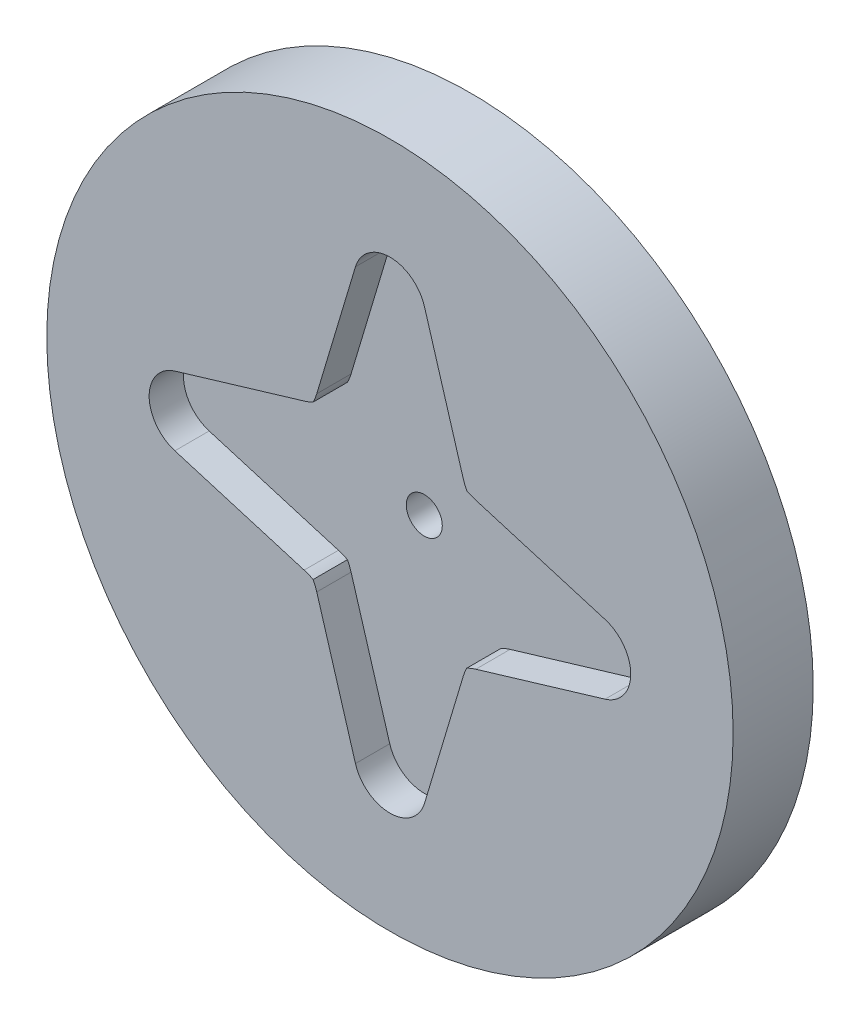
SolidWorks part; units mm, degrees
ref_plane "Front Plane" through (0, 0, 0) normal (0, 0, 1) x (1, 0, 0)
ref_plane "Top Plane" through (0, 0, 0) normal (0, 1, 0) x (1, 0, 0)
ref_plane "Right Plane" through (0, 0, 0) normal (1, 0, 0) x (0, 0, -1)
sketch "Sketch1" plane through (0, 0, 0) normal (0, 0, 1) x (1, 0, 0)
  line L0 (-11.3663, 0) -> (11.3663, 0) construction
  line L1 (-11.9396, 1.916) -> (-4.764, 4.0634)
  line L2 (-11.9396, -1.916) -> (-4.764, -4.0634)
  line L3 (-1.916, 11.9396) -> (-4.0634, 4.764)
  line L4 (1.916, 11.9396) -> (4.0634, 4.764)
  line L5 (11.9396, 1.916) -> (4.764, 4.0634)
  line L6 (11.9396, -1.916) -> (4.764, -4.0634)
  line L7 (1.916, -11.9396) -> (4.0634, -4.764)
  line L8 (-1.916, -11.9396) -> (-4.0634, -4.764)
  line L9 (-19.05, 0) -> (19.05, 0) construction
  circle A0 centre (0, 0) radius 19.05
  arc A1 (-11.9396, -1.916) -> (-11.9396, 1.916) centre (-11.3663, 0) cw
  arc A2 (13.3488, -0.264) -> (13.3488, 0.264) centre (11.3663, 0) ccw
  arc A3 (-4.764, 4.0634) -> (-4.2637, 4.2637) centre (-5.6241, 6.9374) ccw
  arc A4 (-4.764, -4.0634) -> (-4.2637, -4.2637) centre (-5.6241, -6.9374) cw
  arc A5 (-4.0634, 4.764) -> (-4.2637, 4.2637) centre (-6.9374, 5.6241) cw
  arc A6 (-1.916, 11.9396) -> (1.916, 11.9396) centre (0, 11.3663) cw
  arc A7 (4.0634, 4.764) -> (4.2637, 4.2637) centre (6.9374, 5.6241) ccw
  arc A8 (4.764, 4.0634) -> (4.2637, 4.2637) centre (5.6241, 6.9374) cw
  arc A9 (11.9396, 1.916) -> (11.9396, -1.916) centre (11.3663, 0) cw
  arc A10 (4.764, -4.0634) -> (4.2637, -4.2637) centre (5.6241, -6.9374) ccw
  arc A11 (4.0634, -4.764) -> (4.2637, -4.2637) centre (6.9374, -5.6241) cw
  arc A12 (1.916, -11.9396) -> (-1.916, -11.9396) centre (0, -11.3663) cw
  arc A13 (-4.0634, -4.764) -> (-4.2637, -4.2637) centre (-6.9374, -5.6241) ccw
  circle A14 centre (0, 0) radius 1
  point P6 (0, 0)
  point P8 (-13.3663, 0)
  point P11 (13.3663, 0)
  point P48 (0, 0)
  dimension "D1" = 38.1
  dimension "D4" = 7.49
  dimension "D5" = 3
  dimension "D3" = 33.32
  dimension "D7" = 2
  dimension "D2" = 2
  dimension "D6" = 4
extrude "Boss-Extrude1" add sketch "Sketch1" along normal blind 1.905 contours A0 L8 A13 A4 L2 A1 L1 A3 A5 L3 A6 L4 A7 A8 L5 A9 A2 L6 A10 A11 L7 A12 region at (-18.5112, 0, 0)
extrude "Boss-Extrude2" add sketch "Sketch1<3>" against normal blind 2.54 contours A0 L8 A13 A4 L2 A1 L1 A3 A5 L3 A6 L4 A7 A8 L5 A9 A2 L6 A10 A11 L7 A12 | A13 L8 A12 L7 A11 A10 L6 A9 A2 L5 A8 A7 L4 A6 L3 A5 A3 L1 A1 L2 A4 region at (-8.2435, 2.6275, 0) region at (-18.5112, 0, 0)
sketch "Sketch1<3>" plane through (0, 0, 0) normal (0, 0, 1) x (1, 0, 0) same geometry as "Sketch1"
